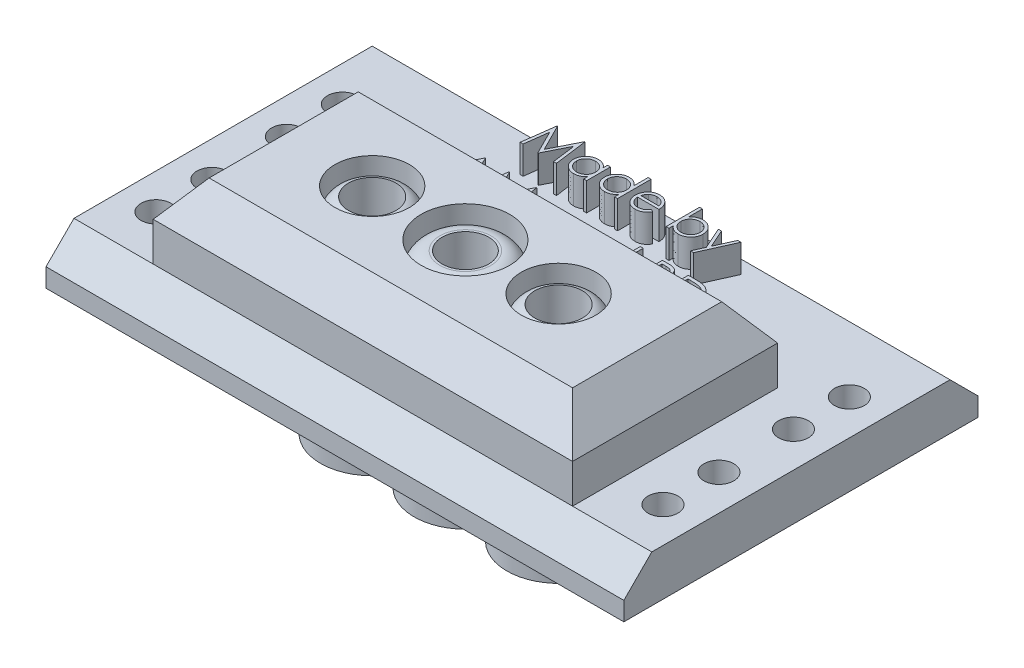
SolidWorks part; units mm, degrees
ref_plane "Alzado" through (0, 0, 0) normal (0, 0, 1) x (1, 0, 0)
ref_plane "Planta" through (0, 0, 0) normal (0, 1, 0) x (1, 0, 0)
ref_plane "Vista lateral" through (0, 0, 0) normal (1, 0, 0) x (0, 0, -1)
sketch "Croquis1" plane through (0, 0, 0) normal (0, 1, 0) x (1, 0, 0)
  line L0 (27.2, -5) -> (27.2, -11) construction
  line L1 (-31, -19) -> (31, -19)
  line L2 (-31, -19) -> (-31, 19)
  line L3 (-31, 19) -> (31, 19)
  line L4 (31, -19) -> (31, 19)
  line L5 (-31, -19) -> (31, 19) construction
  line L6 (-31, 19) -> (31, -19) construction
  line L7 (27.2, -11) -> (-27.2, -11) construction
  line L8 (-27.2, -5) -> (-27.2, -11) construction
  line L9 (27.2, 9) -> (27.2, 3) construction
  line L10 (27.2, 9) -> (27.2, 19) construction
  line L11 (27.2, 9) -> (31, 9) construction
  line L12 (-27.2, 9) -> (-27.2, 3) construction
  line L13 (-27.2, 9) -> (-27.2, 19) construction
  line L14 (0, 0) -> (0, -5) construction
  line L15 (-10, -5) -> (10, -5) construction
  circle A0 centre (27.2, -11) radius 1.6
  circle A1 centre (27.2, -5) radius 1.6
  circle A2 centre (-27.2, -11) radius 1.6
  circle A3 centre (-27.2, -5) radius 1.6
  circle A4 centre (27.2, 9) radius 1.6
  circle A5 centre (27.2, 3) radius 1.6
  circle A6 centre (-27.2, 3) radius 1.6
  circle A7 centre (-27.2, 9) radius 1.6
  circle A8 centre (0, -5) radius 2.5
  circle A9 centre (10, -5) radius 2.55
  circle A10 centre (-10, -5) radius 2.55
  point P0 (0, 0)
  point P31 (0, -5)
  dimension "D4" = 3.2
  dimension "D5" = 3.2
  dimension "D6" = 3.2
  dimension "D7" = 3.2
  dimension "D13" = 3.2
  dimension "D14" = 3.2
  dimension "D20" = 3.2
  dimension "D21" = 3.2
  dimension "D22" = 5
  dimension "D24" = 5.1
  dimension "D25" = 5.1
  dimension "D1" = 62
  dimension "D2" = 38
  dimension "D3" = 6
  dimension "D8" = 6
  dimension "D9" = 54.4
  dimension "D10" = 8
  dimension "D11" = 3.8
  dimension "D12" = 6
  dimension "D15" = 3.8
  dimension "D16" = 10
  dimension "D17" = 6
  dimension "D18" = 10
  dimension "D19" = 3.8
  dimension "D23" = 14
  dimension "D26" = 10
extrude "Saliente-Extruir1" add sketch "Croquis1" along normal blind 5
sketch "Croquis2" plane through (0, 5, 0) normal (0, 1, 0) x (1, 0, 0)
  line L0 (-31, -19) -> (31, -19) construction
  line L1 (0, -5) -> (0, 0) construction
  circle A0 centre (0, -5) radius 4.75
  circle A1 centre (0, -5) radius 2.5
  dimension "D2" = 9.5
  dimension "D3" = 5
  dimension "D1" = 14
extrude "Saliente-Extruir2" add sketch "Croquis2" along normal blind 7
fillet "Redondeo2" radius 2 1 edges at (0, 12, 9.75)
sketch "Croquis4" plane through (0, 5, 0) normal (0, 1, 0) x (1, 0, 0)
  line L0 (0, -5) -> (-10, -5) construction
  line L1 (0, -5) -> (10, -5) construction
  circle A0 centre (10, -5) radius 2.55
  circle A1 centre (-10, -5) radius 2.55
  circle A2 centre (-10, -5) radius 4
  circle A3 centre (10, -5) radius 4
  circle A4 centre (0, -5) radius 2.5 construction
  dimension "D1" = 5.1
  dimension "D2" = 5.1
  dimension "D5" = 8
  dimension "D6" = 8
  dimension "D3" = 10
  dimension "D4" = 10
extrude "Saliente-Extruir3" add sketch "Croquis4" along normal blind 7
fillet "Redondeo3" radius 2 2 edges at (-10, 12, 9) (10, 12, 9)
chamfer "Chaflán1" distance 3 angle 45 2 edges at (0, 5, -19) (0, 5, 19)
sketch "Croquis5" plane through (0, 5, 0) normal (0, 1, 0) x (1, 0, 0)
  line L1 (-22.5, 6) -> (22.5, 6)
  line L2 (-22.5, 6) -> (-22.5, -16)
  line L3 (-22.5, -16) -> (22.5, -16)
  line L4 (22.5, 6) -> (22.5, -16)
  line L5 (-22.5, 6) -> (22.5, -16) construction
  line L6 (-22.5, -16) -> (22.5, 6) construction
  line L7 (-16.5, 2) -> (16.5, 2)
  line L8 (-16.5, 2) -> (-16.5, -12)
  line L9 (-16.5, -12) -> (16.5, -12)
  line L10 (16.5, 2) -> (16.5, -12)
  line L11 (-16.5, 2) -> (16.5, -12) construction
  line L12 (-16.5, -12) -> (16.5, 2) construction
  point P0 (0, -5)
  point P6 (0, -5)
  point P11 (14.772, -10.5492)
  point P12 (16.017, -9.75)
  point P13 (16, -11.4926)
  point P17 (16, -9.7498)
  point P18 (16, -9.7498)
  circle M7 centre (-10, -5) radius 4
  circle M20 centre (0, -5) radius 4.75
  circle M21 centre (10, -5) radius 4
  dimension "D1" = 45
  dimension "D2" = 22
  dimension "D3" = 6
  dimension "D4" = 4
extrude "Saliente-Extruir4" add sketch "Croquis5" along normal blind 8 separate body contours L4 L1 L2 L3 L7 L10 L9 L8 | L8 L9 L7 M20 M7 | L10 L7 L9 M20 M21 region at (0, 5, -5.4991) region at (0, 5, -1.6415)
sketch "Croquis8" plane through (0, 5, 0) normal (0, 1, 0) x (1, 0, 0)
  line L0 (0, 0) -> (0, 12) construction
  line L1 (-14, 12) -> (14, 12) construction
  text T0 "Made by \r\nAM and BD"
  point P6 (0, 12)
  dimension "D1" = 28
  dimension "D2" = 12
extrude "Saliente-Extruir5" add sketch "Croquis8" along normal blind 3
sketch "Croquis9" plane through (0, 0, 0) normal (0, -1, 0) x (1, 0, 0)
  line L0 (0, -6.6) -> (0, 6.6) construction
  circle A0 centre (0, 5) radius 5.5
  circle A1 centre (0, 5) radius 2.5 construction
  circle A2 centre (10, 5) radius 5.55
  circle A3 centre (10, 5) radius 2.55 construction
  circle A4 centre (-10, 5) radius 5.55
  circle M1 centre (10, 5) radius 2.55
  circle M14 centre (0, 5) radius 2.5
  circle M15 centre (-10, 5) radius 2.55
  dimension "D1" = 3
  dimension "D2" = 3
extrude "Saliente-Extruir7" add sketch "Croquis9" along normal blind 10 contours A0 A2 M1 | A0 A4 A2 M14 | A4 A0 M15 | A0 A2 | A4 A0 region at (4.9745, 0, 5) region at (5.5161, 0, 6.2381) region at (4.3017, 0, 5) region at (-4.9745, 0, 5) region at (-5.6533, 0, 5)
chamfer "Chaflán2" distance 3 angle 52 4 edges at (22.5, 13, 5) (-22.5, 13, 5) (0, 13, -6) (0, 13, 16) first distance on face at (0, 13, 5)
